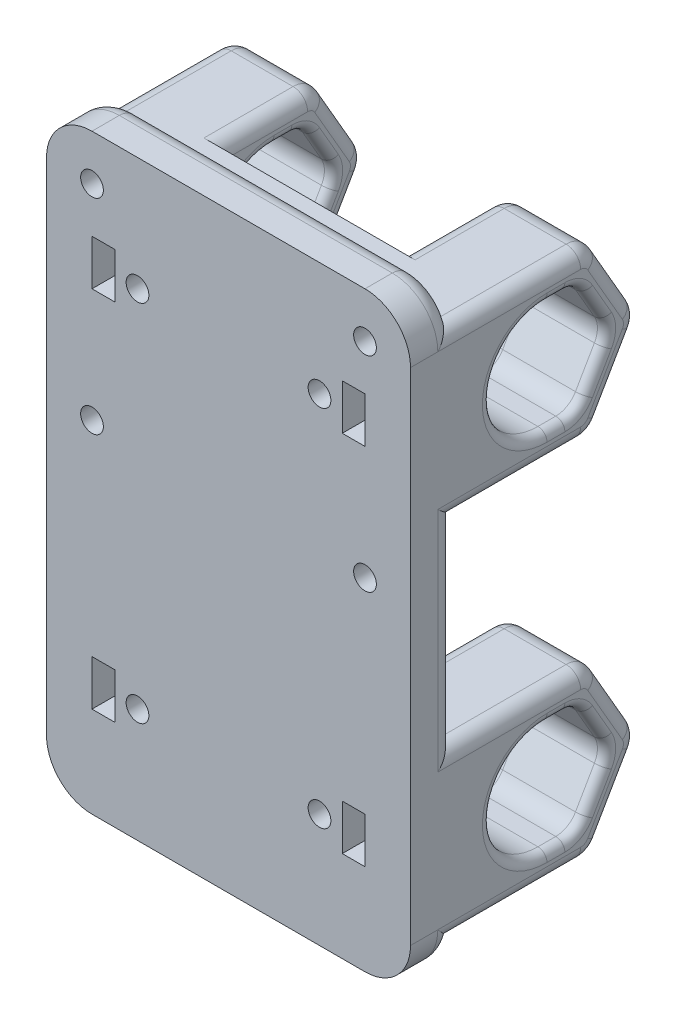
SolidWorks part; units mm, degrees
ref_plane "Спереди" through (0, 0, 0) normal (0, 0, 1) x (1, 0, 0)
ref_plane "Сверху" through (0, 0, 0) normal (0, 1, 0) x (1, 0, 0)
ref_plane "Справа" through (0, 0, 0) normal (1, 0, 0) x (0, 0, -1)
sketch "Эскиз1" plane through (0, 0, 0) normal (1, 0, 0) x (0, 0, -1)
  line L0 (-30.5769, 0) -> (38.4615, 0) construction
  line L1 (0, 32.5) -> (0, -32.5)
  line L2 (0, 32.5) -> (5, 32.5)
  line L3 (5, 32.5) -> (5, 29.1)
  line L4 (5, -32.5) -> (0, -32.5)
  line L5 (-35.9615, 20) -> (79.0385, 20) construction
  line L6 (21.9282, 20) -> (18.4064, 26.1)
  line L7 (21.9282, 20) -> (18.4064, 13.9)
  line L8 (15, 13.9) -> (18.4064, 13.9)
  line L9 (15, 26.1) -> (18.4064, 26.1)
  line L10 (5, 29.1) -> (20.1384, 29.1)
  line L11 (20.1384, 29.1) -> (25.3923, 20)
  line L12 (25.3923, 20) -> (20.1384, 10.9)
  line L13 (20.1384, 10.9) -> (5, 10.9)
  line L14 (5, 10.9) -> (5, -10.9)
  line L15 (25.3923, -20) -> (20.1384, -10.9)
  line L16 (20.1384, -10.9) -> (5, -10.9)
  line L17 (15, -13.9) -> (18.4064, -13.9)
  line L18 (21.9282, -20) -> (18.4064, -13.9)
  line L19 (20.1384, -29.1) -> (25.3923, -20)
  line L20 (15, -26.1) -> (18.4064, -26.1)
  line L21 (21.9282, -20) -> (18.4064, -26.1)
  line L22 (5, -29.1) -> (20.1384, -29.1)
  line L23 (5, -29.1) -> (5, -32.5)
  circle A0 centre (15, 20) radius 6 construction
  arc A1 (15, 26.1) -> (15, 13.9) centre (15, 20) ccw
  circle A2 centre (15, -20) radius 6 construction
  arc A3 (15, -26.1) -> (15, -13.9) centre (15, -20) cw
  point P6 (0, 0)
  dimension "D5" = 12
  dimension "D6" = 12.2
  dimension "D1" = 5
  dimension "D2" = 65
  dimension "D3" = 20
  dimension "D4" = 10
  dimension "D7" = 60
  dimension "D8" = 3
  dimension "D9" = 3
  dimension "D10" = 3
extrude "Бобышка-Вытянуть1" add sketch "Эскиз1" along normal mid plane 40
fillet "Скругление1" radius 5 4 edges at (20, -32.5, -2.5) (-20, -32.5, -2.5) (-20, 32.5, -2.5) (20, 32.5, -2.5)
fillet "Скругление2" radius 2.5 12 edges at (0, -26.1, -18.4064) (0, -29.1, -20.1384) (0, -20, -25.3923) (0, -20, -21.9282) (0, -13.9, -18.4064) (0, -10.9, -20.1384) (0, 29.1, -20.1384) (0, 20, -25.3923) (0, 10.9, -20.1384) (0, 13.9, -18.4064) (0, 20, -21.9282) (0, 26.1, -18.4064)
sketch "Эскиз2" plane through (0, 29.1, 0) normal (0, 1, 0) x (1, 0, 0)
  line L0 (0, 27.6977) -> (0, -2.652) construction
  line L2 (-10, 28.9) -> (10, 28.9)
  line L3 (-10, 28.9) -> (-10, 8.9)
  line L4 (-10, 8.9) -> (10, 8.9)
  line L5 (10, 28.9) -> (10, 8.9)
  line L6 (-10, 28.9) -> (10, 8.9) construction
  line L7 (-10, 8.9) -> (10, 28.9) construction
  point P1 (0, 18.9)
  dimension "D1" = 20
  dimension "D2" = 8.9
  dimension "D3" = 20
extrude "Вырез-Вытянуть1" cut sketch "Эскиз2" against normal through all
fillet "Скругление4" radius 2 8 edges at (17.9155, -31.562, -5) (-17.9155, -31.562, -5) (17.9155, 31.562, -5) (-17.9155, 31.562, -5) (0, -32.5, -5) (20, 0, -5) (-20, 0, -5) (0, 32.5, -5)
fillet "Скругление5" radius 1.6 60 edges at (-20, 24.375, -22.8664) (-20, 10.9, -10.8475) (-20, 11.2349, -19.945) (-20, 15.45, -22.7654) (-10, 10.9, -13.7975) (-10, 11.2349, -19.945) (-10, 15.45, -22.7654) (-10, 29.1, -13.7975) (-10, 28.7651, -19.945) (-10, 24.55, -22.7654) (10, 29.1, -13.7975) (10, 28.7651, -19.945) (10, 24.55, -22.7654) (10, 10.9, -13.7975) (10, 11.2349, -19.945) (10, 15.45, -22.7654) (20, 10.9, -10.8475) (20, 11.2349, -19.945) (20, 15.45, -22.7654) (20, 24.375, -22.8664) (-20, -10.9, -10.8475) (-20, -11.2349, -19.945) (-20, -15.45, -22.7654) (-20, -24.375, -22.8664) (-10, -29.1, -13.7975) (-10, -28.7651, -19.945) (-10, -24.55, -22.7654) (-10, -10.9, -13.7975) (-10, -11.2349, -19.945) (-10, -15.45, -22.7654) (10, -10.9, -13.7975) (10, -11.2349, -19.945) (10, -15.45, -22.7654) (10, -29.1, -13.7975) (10, -28.7651, -19.945) (10, -24.55, -22.7654) (20, -24.375, -22.8664) (20, -10.9, -10.8475) (20, -11.2349, -19.945) (20, -15.45, -22.7654) (-20, 20, -25.0056) (-10, 20, -25.0056) (10, 20, -25.0056) (20, 20, -25.0056) (-20, -20, -25.0056) (-10, -20, -25.0056) (10, -20, -25.0056) (20, -20, -25.0056) (-19.7371, 29.1, -10.8475) (-19.8813, 28.5829, -20.2175) (-19.9969, 27.6751, -20.9611) (19.7371, 29.1, -10.8475) (19.9003, 28.4936, -20.3274) (19.9969, 27.6751, -20.9611) (-19.7371, -29.1, -10.8475) (-19.9003, -28.4936, -20.3274) (-19.9969, -27.6751, -20.9611) (19.7371, -29.1, -10.8475) (19.8813, -28.5829, -20.2175) (19.9969, -27.6751, -20.9611)
fillet "Скругление6" radius 1 68 edges at (-10, -23.05, -20.1673) (-10, -25.7651, -18.213) (-10, -26.1, -15.9815) (-10, -24.3134, -10.6866) (-10, -15.6866, -10.6866) (-10, -13.9, -15.9815) (-10, -14.2349, -18.213) (-10, -16.95, -20.1673) (20, -16.95, -20.1673) (20, -14.2349, -18.213) (20, -13.9, -15.9815) (20, -20, -8.9) (20, -26.1, -15.9815) (20, -25.7651, -18.213) (20, -23.05, -20.1673) (-10, 16.95, -20.1673) (-10, 14.2349, -18.213) (-10, 13.9, -15.9815) (-10, 15.6866, -10.6866) (-10, 24.3134, -10.6866) (-10, 26.1, -15.9815) (-10, 25.7651, -18.213) (-10, 23.05, -20.1673) (20, 23.05, -20.1673) (20, 25.7651, -18.213) (20, 26.1, -15.9815) (20, 20, -8.9) (20, 13.9, -15.9815) (20, 14.2349, -18.213) (20, 16.95, -20.1673) (-10, -20, -21.5415) (20, -20, -21.5415) (-10, 20, -21.5415) (20, 20, -21.5415) (-20, 16.95, -20.1673) (-20, 14.2349, -18.213) (-20, 13.9, -15.9815) (-20, 20, -8.9) (-20, 26.1, -15.9815) (-20, 25.7651, -18.213) (-20, 23.05, -20.1673) (-20, -23.05, -20.1673) (-20, -25.7651, -18.213) (-20, -26.1, -15.9815) (-20, -20, -8.9) (-20, -13.9, -15.9815) (-20, -14.2349, -18.213) (-20, -16.95, -20.1673) (10, -16.95, -20.1673) (10, -14.2349, -18.213) (10, -13.9, -15.9815) (10, -15.6866, -10.6866) (10, -24.3134, -10.6866) (10, -26.1, -15.9815) (10, -25.7651, -18.213) (10, -23.05, -20.1673) (10, 23.05, -20.1673) (10, 25.7651, -18.213) (10, 26.1, -15.9815) (10, 24.3134, -10.6866) (10, 15.6866, -10.6866) (10, 13.9, -15.9815) (10, 14.2349, -18.213) (10, 16.95, -20.1673) (-20, 20, -21.5415) (-20, -20, -21.5415) (10, -20, -21.5415) (10, 20, -21.5415)
ref_plane "Плоскость1" through (0, -20, 0) normal (0, 1, 0) x (1, 0, 0)
sketch "Эскиз3" plane through (0, -20, 0) normal (0, 1, 0) x (1, 0, 0)
  line L0 (0, 0) -> (0, 14.8981) construction
  line L2 (-15, 15) -> (15, 15)
  line L3 (15, 15) -> (15, 0)
  line L4 (15, 0) -> (-15, 0) construction
  line L5 (15, 0) -> (12.5, 0)
  line L6 (12.5, 0) -> (12.5, 3)
  line L7 (12.5, 3) -> (-12.5, 3)
  line L8 (-12.5, 3) -> (-12.5, 0)
  line L9 (-12.5, 0) -> (-15, 0)
  line L10 (-15, 0) -> (-15, 15)
  point P1 (0, 15)
  dimension "D1" = 30
  dimension "D2" = 15
  dimension "D3" = 3
  dimension "D4" = 2.5
extrude "Вырез-Вытянуть2" cut sketch "Эскиз3" against normal mid plane 5
sketch "Эскиз7" plane through (0, 0, -3) normal (0, 0, -1) x (-1, 0, 0)
  line L0 (12.5, -22.5) -> (-12.5, -22.5) construction
  line L1 (12.5, -17.5) -> (7.5, -17.5)
  line L2 (12.5, -17.5) -> (12.5, -22.5)
  line L3 (12.5, -22.5) -> (7.5, -22.5)
  line L4 (7.5, -17.5) -> (7.5, -22.5)
  line L5 (7.5, -22.5) -> (12.5, -17.5) construction
  line L7 (-12.5, -17.5) -> (-7.5, -17.5)
  line L8 (-12.5, -17.5) -> (-12.5, -22.5)
  line L9 (-12.5, -22.5) -> (-7.5, -22.5)
  line L10 (-7.5, -17.5) -> (-7.5, -22.5)
  line L11 (-12.5, -22.5) -> (-7.5, -17.5) construction
  line L12 (-10, -20) -> (10, -20) construction
  circle A0 centre (10, -20) radius 1.25
  circle A1 centre (-10, -20) radius 1.25
  circle A2 centre (0, -20) radius 2
  dimension "D2" = 2.5
  dimension "D4" = 2.5
  dimension "D5" = 4
  dimension "D1" = 5
  dimension "D3" = 5
extrude "Бобышка-Вытянуть2" add sketch "Эскиз7" along normal blind 1 contours L3 L4 L1 L2 | L10 L9 L8 L7
extrude "Вырез-Вытянуть7" cut sketch "Эскиз7<5>" against normal through all from offset 1 contours A1 | A0
sketch "Эскиз7<5>" plane through (0, 0, -3) normal (0, 0, -1) x (-1, 0, 0) same geometry as "Эскиз7"
extrude "Вырез-Вытянуть8" cut sketch "Эскиз7<6>" against normal blind 1 contours A2
sketch "Эскиз7<6>" plane through (0, 0, -3) normal (0, 0, -1) x (-1, 0, 0) same geometry as "Эскиз7"
mirror "Зеркальное отражение1" about plane through (0, 0, 0) normal (0, 1, 0) of "Вырез-Вытянуть8", "Вырез-Вытянуть7", "Бобышка-Вытянуть2", "Вырез-Вытянуть2"
sketch "Эскиз5" plane through (0, 0, 0) normal (0, 0, 1) x (1, 0, 0)
  circle A0 centre (-15, 27.5) radius 1.25
  circle A1 centre (-15, 5) radius 1.25
  circle A2 centre (15, 27.5) radius 1.25
  circle A3 centre (15, 5) radius 1.25
  dimension "D1" = 2.5
  dimension "D2" = 2.5
  dimension "D3" = 2.5
  dimension "D4" = 2.5
extrude "Вырез-Вытянуть5" cut sketch "Эскиз5" against normal blind 4
sketch "Эскиз8" plane through (0, 0, -5) normal (0, 0, -1) x (-1, 0, 0)
  line L0 (-18, 2.04) -> (18, 2.04) construction
  line L1 (-18, 10.9) -> (-18, -10.9) construction
  line L2 (18, -10.9) -> (18, 10.9) construction
  line L3 (-18, 10.9) -> (18, 10.9) construction
  circle A0 centre (-5, 2.04) radius 1.25
  circle A1 centre (5, 2.04) radius 1.25
  point P12 (0, 2.04)
  dimension "D4" = 2.5
  dimension "D5" = 2.5
  dimension "D1" = 8.86
  dimension "D2" = 5
  dimension "D3" = 5
extrude "Вырез-Вытянуть9" cut sketch "Эскиз8" against normal blind 4
